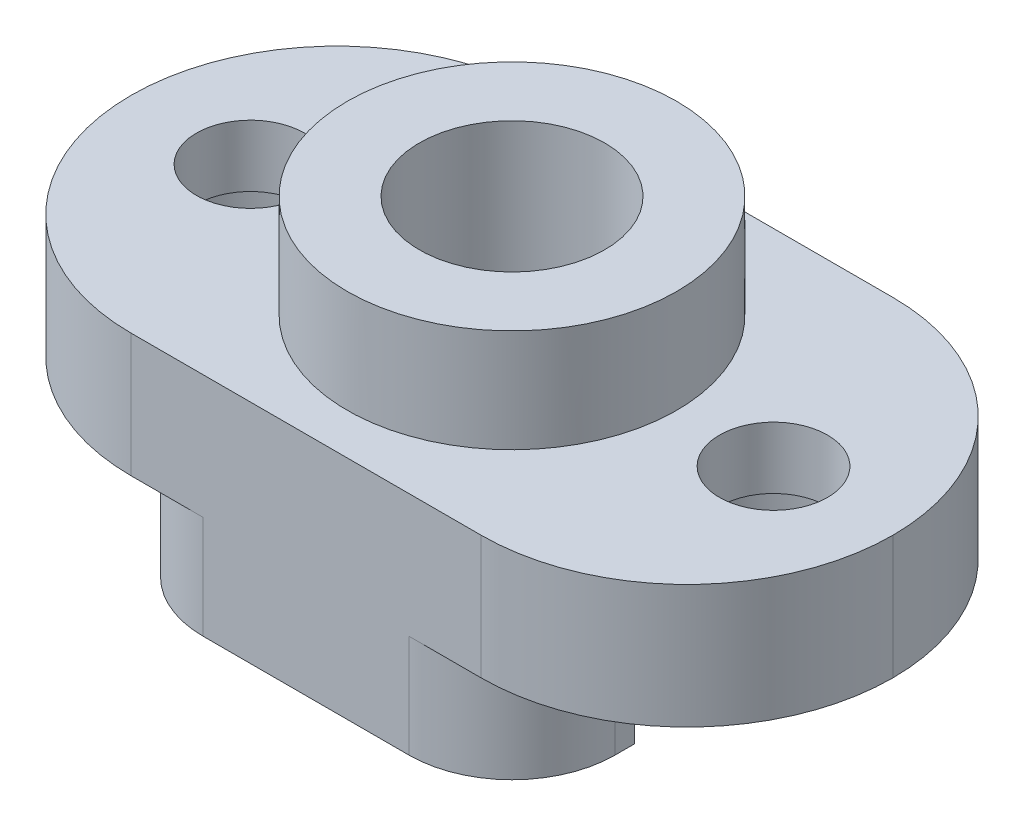
SolidWorks part; units mm, degrees
material "ABS"
ref_plane "Front Plane" through (0, 0, 0) normal (0, 0, 1) x (1, 0, 0)
ref_plane "Top Plane" through (0, 0, 0) normal (0, 1, 0) x (1, 0, 0)
ref_plane "Right Plane" through (0, 0, 0) normal (1, 0, 0) x (0, 0, -1)
sketch "Sketch1" plane through (0, 0, 0) normal (0, 1, 0) x (1, 0, 0)
  line L1 (-5, -10) -> (5, -10)
  line L2 (-10, -5) -> (-10, 5)
  line L3 (-5, 10) -> (5, 10)
  line L4 (10, -5) -> (10, 5)
  line L5 (-10, -10) -> (10, 10) construction
  line L6 (-10, 10) -> (10, -10) construction
  arc A0 (-5, -10) -> (-10, -5) centre (-5, -5) cw
  arc A1 (5, -10) -> (10, -5) centre (5, -5) ccw
  arc A2 (5, 10) -> (10, 5) centre (5, 5) cw
  arc A3 (-10, 5) -> (-5, 10) centre (-5, 5) cw
  point P0 (0, 0)
  dimension "D1" = 20
  dimension "D3" = 5
  dimension "D2" = 20
extrude "Boss-Extrude1" add sketch "Sketch1" against normal blind 11
sketch "Sketch2" plane through (0, 0, 0) normal (0, 1, 0) x (1, 0, 0)
  line L1 (-18.5, 10) -> (18.5, 10)
  line L2 (-18.5, 10) -> (-18.5, -10)
  line L3 (-18.5, -10) -> (18.5, -10)
  line L4 (18.5, 10) -> (18.5, -10)
  line L5 (-18.5, 10) -> (18.5, -10) construction
  line L6 (-18.5, -10) -> (18.5, 10) construction
  point P0 (0, 0)
  dimension "D1" = 20
  dimension "D2" = 37
extrude "Boss-Extrude2" add sketch "Sketch2" against normal blind 6
sketch "Sketch8" plane through (0, 0, 0) normal (0, 1, 0) x (1, 0, 0)
  circle A0 centre (0, 0) radius 8
  dimension "D1" = 16
extrude "Boss-Extrude3" add sketch "Sketch8" along normal blind 5
sketch "Sketch4" plane through (0, -6, 0) normal (0, -1, 0) x (-1, 0, 0)
  line L0 (0, 18.1422) -> (0, -21.6348) construction
  circle A0 centre (-12.7, 0) radius 4.875
  circle A2 centre (12.7, 0) radius 4.875
  dimension "D2" = 9.75
  dimension "D1" = 12.7
extrude "Cut-Extrude1" cut sketch "Sketch4" against normal blind 3 and the other way through all
sketch "Sketch5" plane through (0, -6, 0) normal (0, -1, 0) x (-1, 0, 0)
  line L0 (0, 17.8835) -> (0, -22.605) construction
  circle A0 centre (-12.7, 0) radius 2.625
  circle A1 centre (12.7, 0) radius 2.625
  dimension "D1" = 5.25
extrude "Cut-Extrude2" cut sketch "Sketch5" against normal through all
sketch "Sketch6" plane through (0, -11, 0) normal (0, -1, 0) x (1, 0, 0)
  line L1 (7, -4.0415) -> (7, 4.0415)
  line L2 (7, 4.0415) -> (0, 8.0829)
  line L3 (0, 8.0829) -> (-7, 4.0415)
  line L4 (-7, 4.0415) -> (-7, -4.0415)
  line L5 (-7, -4.0415) -> (0, -8.0829)
  line L6 (0, -8.0829) -> (7, -4.0415)
  circle A0 centre (0, 0) radius 7 construction
  dimension "D1" = 14
extrude "Cut-Extrude3" cut sketch "Sketch6" against normal blind 6
sketch "Sketch7" plane through (0, -5, 0) normal (0, -1, 0) x (1, 0, 0)
  circle A0 centre (0, 0) radius 4.5
  dimension "D1" = 9
extrude "Cut-Extrude4" cut sketch "Sketch7" against normal through all
fillet "Fillet2" radius 10 4 edges at (-18.5, -3, 10) (-18.5, -3, -10) (18.5, -3, -10) (18.5, -3, 10)
